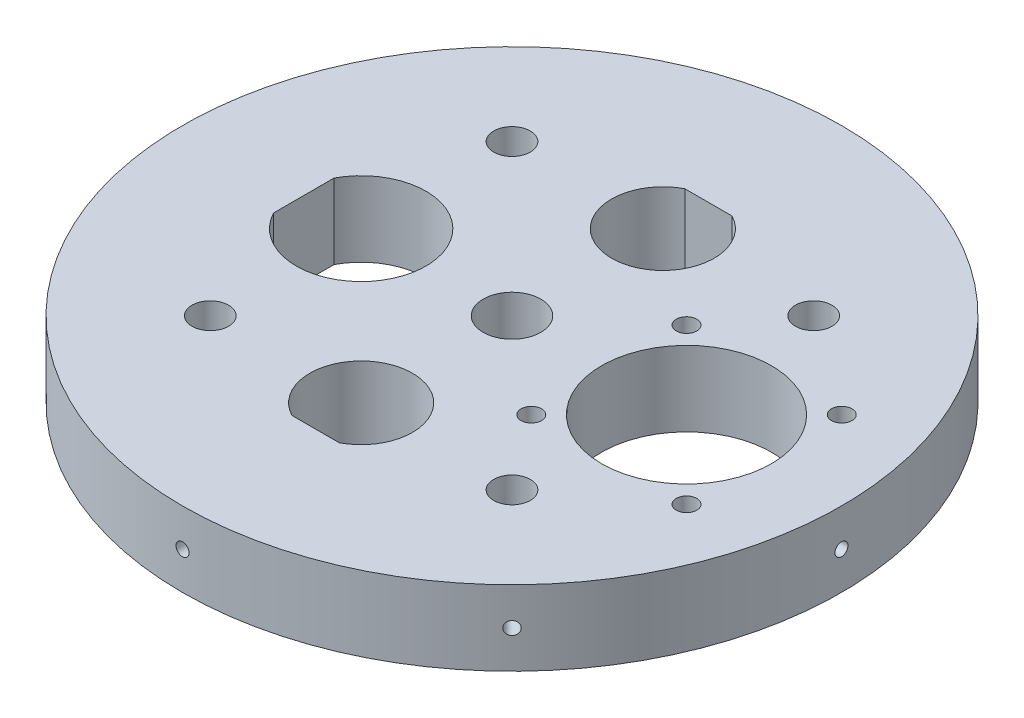
SolidWorks part; units mm, degrees
ref_plane "Front Plane" through (0, 0, 0) normal (0, 0, 1) x (1, 0, 0)
ref_plane "Top Plane" through (0, 0, 0) normal (0, 1, 0) x (1, 0, 0)
ref_plane "Right Plane" through (0, 0, 0) normal (1, 0, 0) x (0, 0, -1)
sketch "Sketch2" plane through (0, 0, 0) normal (0, 1, 0) x (1, 0, 0)
  circle A0 centre (0, 0) radius 57.15
  dimension "D1" = 114.3
extrude "Boss-Extrude1" add sketch "Sketch2" along normal blind 13 contours A0
sketch "Sketch6" plane through (0, 13, 0) normal (0, 1, 0) x (1, 0, 0)
  circle A0 centre (-26.1629, -26.1629) radius 3.175
  circle A1 centre (26.1629, -26.1629) radius 3.175
  circle A2 centre (-26.1629, 26.1631) radius 3.175
  circle A3 centre (26.1629, 26.1631) radius 3.175
  dimension "D1" = 6.35
  dimension "D2" = 74
  dimension "D3" = 26.1629
  dimension "D4" = 26.1629
  dimension "D5" = 26.1629
extrude "Cut-Extrude1" cut sketch "Sketch6" against normal up to next
sketch "Sketch7" plane through (0, 13, 0) normal (0, 1, 0) x (1, 0, 0)
  circle A0 centre (30, 0.2699) radius 14.732
  circle A3 centre (16.54, -13.1941) radius 1.778
  circle A4 centre (16.54, 13.7299) radius 1.778
  circle A5 centre (43.46, 13.7299) radius 1.778
  circle A6 centre (43.46, -13.1941) radius 1.778
  dimension "D1" = 29.464
  dimension "D2" = 3.556
  dimension "D3" = 3.556
  dimension "D4" = 3.556
  dimension "D5" = 3.556
  dimension "D6" = 13.46
  dimension "D7" = 13.46
  dimension "D8" = 13.46
  dimension "D9" = 13.464
  dimension "D10" = 30
extrude "Cut-Extrude2" cut sketch "Sketch7" against normal through all
sketch "Sketch8" plane through (0, 13, 0) normal (0, 1, 0) x (1, 0, 0)
  line L0 (4.0988, 34.0631) -> (-4.0988, 34.0631)
  line L1 (4.0988, -34.0629) -> (-4.0988, -34.0629)
  line L2 (-36.1129, 5.2498) -> (-36.1129, -5.2498)
  arc A0 (4.0988, -34.0629) -> (-4.0988, -34.0629) centre (0, -26.1629) ccw
  arc A1 (-4.0988, 34.0631) -> (4.0988, 34.0631) centre (0, 26.1631) ccw
  circle A2 centre (0, 0) radius 5
  arc A3 (-36.1129, -5.2498) -> (-36.1129, 5.2498) centre (-26.1629, 0) ccw
  circle A4 centre (26.1629, -26.1629) radius 3.175 construction
  circle A5 centre (26.1629, 26.1631) radius 3.175 construction
  circle A6 centre (-26.1629, -26.1629) radius 3.175 construction
  dimension "D1" = 17.8
  dimension "D2" = 17.8
  dimension "D3" = 10
  dimension "D4" = 22.5
  dimension "D5" = 7.9
  dimension "D6" = 0
  dimension "D7" = 7.9
  dimension "D8" = 0
  dimension "D9" = 9.95
  dimension "D10" = 0
extrude "Cut-Extrude3" cut sketch "Sketch8" against normal through all
sketch "Sketch10" plane through (0, 13, 0) normal (0, 1, 0) x (1, 0, 0)
  circle A0 centre (-26.1629, 26.1631) radius 7.9375
  circle A1 centre (26.1631, 26.1629) radius 7.9375
  circle A2 centre (26.1629, -26.1631) radius 7.9375
  circle A3 centre (-26.1631, -26.1629) radius 7.9375
  point P11 (0, 0)
  dimension "D1" = 4
sketch "Sketch11" plane through (0, 13, 0) normal (0, 1, 0) x (1, 0, 0)
  circle A0 centre (0, 0) radius 10
ref_plane "Plane1" through (0, 0, -57.15) normal (0, 0, -1) x (-1, 0, 0)
sketch "Sketch12" plane through (0, 0, -57.15) normal (0, 0, -1) x (-1, 0, 0)
  line L0 (57.15, 0) -> (57.15, 13) construction
  point P0 (0, 6.5)
  point P1 (57.15, 6.5)
hole_wizard "#4-40 Tapped Hole2" positions "3DSketch7" profile "Sketch16" tap size "#4-40" standard "ANSI Inch"
sketch3d "3DSketch7"
  point P0 (0, 6.5, -57.15)
sketch "Sketch16" plane through (0, 6.5, -57.15) normal (1, 0, 0) x (0, 1, 0)
  line L0 (0, 0) -> (0, 10.6792)
  line L1 (0, 10.6792) -> (1.1303, 10)
  line L2 (1.1303, 10) -> (1.1303, 0)
  line L5 (1.1303, 0) -> (0, 0)
  line L10 (0, 10.6792) -> (-1.1303, 10) construction
  line L11 (0, -6.35) -> (0, 107.95) construction
  dimension "Tap Drill Dia." = 2.2606
  dimension "Tap Drill Depth" = 10
  dimension "Drill Angle" = 118
cosmetic thread "Hole Thread2" parameters "D1"=5.69, "D2"=2.8448
pattern_circular "CirPattern1" count 8 over 360 about axis through (0, 0, 0) along (0, 1, 0) of "#4-40 Tapped Hole2"
cosmetic thread "Hole Thread3" parameters "D1"=5.69, "D2"=2.8448
cosmetic thread "Hole Thread4" parameters "D1"=5.69, "D2"=2.8448
cosmetic thread "Hole Thread5" parameters "D1"=5.69, "D2"=2.8448
cosmetic thread "Hole Thread6" parameters "D1"=5.69, "D2"=2.8448
cosmetic thread "Hole Thread7" parameters "D1"=5.69, "D2"=2.8448
cosmetic thread "Hole Thread8" parameters "D1"=5.69, "D2"=2.8448
cosmetic thread "Hole Thread9" parameters "D1"=5.69, "D2"=2.8448
equation "\"width\"=26.1629"
equation "\"D4@Sketch6\"=\"width\""
equation "\"D3@Sketch6\"=\"width\""
equation "\"D5@Sketch6\"=\"width\""
